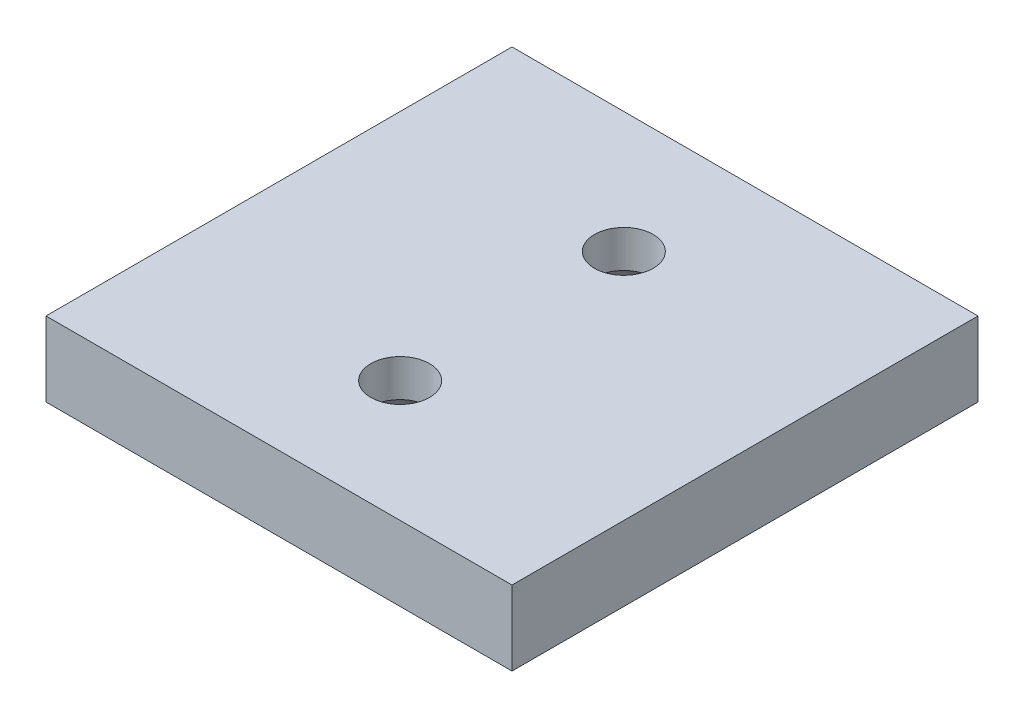
SolidWorks part; units mm, degrees
ref_plane "Front Plane" through (0, 0, 0) normal (0, 0, 1) x (1, 0, 0)
ref_plane "Top Plane" through (0, 0, 0) normal (0, 1, 0) x (1, 0, 0)
ref_plane "Right Plane" through (0, 0, 0) normal (1, 0, 0) x (0, 0, -1)
sketch "Sketch1" plane through (0, 0, 0) normal (0, 1, 0) x (1, 0, 0)
  line L0 (-25, 0) -> (25, 0) construction
  line L1 (-25, 25) -> (25, 25)
  line L2 (-25, 25) -> (-25, -25)
  line L3 (-25, -25) -> (25, -25)
  line L4 (25, 25) -> (25, -25)
  point P0 (0, 0)
  dimension "D1" = 50
  dimension "D2" = 50
extrude "Boss-Extrude1" add sketch "Sketch1" along normal blind 8
sketch "Sketch2" plane through (0, 0, 0) normal (0, 1, 0) x (1, 0, 0)
  line L0 (-15.2934, 0) -> (18.7691, 0) construction
  circle A0 centre (0, -12) radius 6
  circle A1 centre (0, 12) radius 6
  dimension "D2" = 12
  dimension "D1" = 12
extrude "Cut-Extrude2" cut sketch "Sketch2" along normal blind 4
sketch "Sketch4" plane through (0, 4, 0) normal (0, -1, 0) x (1, 0, 0)
  line L0 (13.0733, 0) -> (-10.6003, 0) construction
  circle A0 centre (0, -12) radius 3.15
  circle A1 centre (0, 12) radius 3.15
  dimension "D1" = 6.3
extrude "Cut-Extrude3" cut sketch "Sketch4" against normal blind 4
fillet "Fillet1" radius 4 2 edges at (0, 4, 18) (0, 4, -18)
